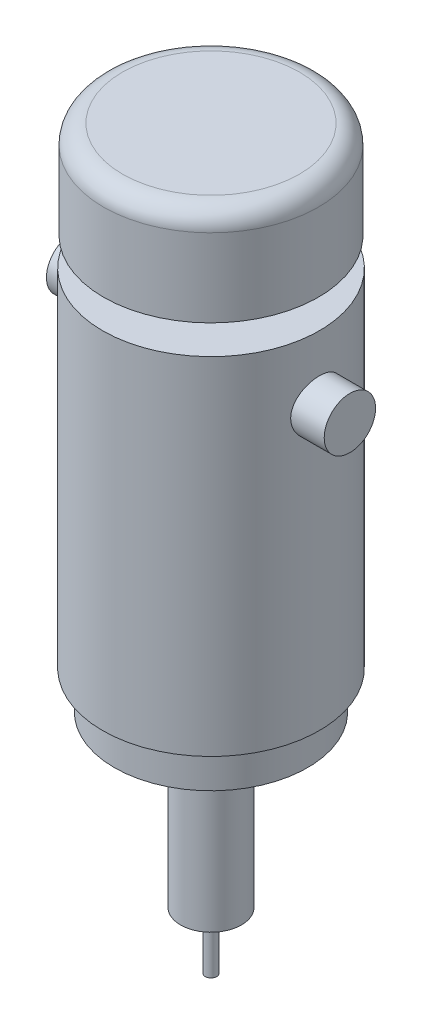
SolidWorks part; units mm, degrees
ref_plane "Front Plane" through (0, 0, 0) normal (0, 0, 1) x (1, 0, 0)
ref_plane "Top Plane" through (0, 0, 0) normal (0, 1, 0) x (1, 0, 0)
ref_plane "Right Plane" through (0, 0, 0) normal (1, 0, 0) x (0, 0, -1)
sketch "Sketch1" plane through (0, 0, 0) normal (0, 1, 0) x (1, 0, 0)
  circle A0 centre (0, 0) radius 28.5
  dimension "D1" = 57
extrude "Boss-Extrude1" add sketch "Sketch1" along normal mid plane 91
sketch "Sketch4" plane through (0, -45.5, 0) normal (0, -1, 0) x (1, 0, 0)
  circle A0 centre (0, 0) radius 25.4
  dimension "D1" = 50.8
extrude "Boss-Extrude4" add sketch "Sketch4" along normal blind 10
sketch "Sketch5" plane through (0, -55.5, 0) normal (0, -1, 0) x (1, 0, 0)
  circle A0 centre (0, 0) radius 12.65
  dimension "D1" = 25.3
extrude "Boss-Extrude5" add sketch "Sketch5" along normal blind 2.5
sketch "Sketch2" plane through (0, -58, 0) normal (0, -1, 0) x (1, 0, 0)
  circle A0 centre (0, 0) radius 8
  dimension "D1" = 16
extrude "Boss-Extrude2" add sketch "Sketch2" along normal blind 42
sketch "Sketch6" plane through (0, 45.5, 0) normal (0, 1, 0) x (1, 0, 0)
  circle A0 centre (0, 0) radius 4
  dimension "D1" = 8
extrude "Boss-Extrude6" add sketch "Sketch6" along normal blind 33
sketch "Sketch7" plane through (0, 78.5, 0) normal (0, 1, 0) x (1, 0, 0)
  circle A0 centre (0, 0) radius 28.25
  dimension "D1" = 56.5
extrude "Boss-Extrude7" add sketch "Sketch7" against normal blind 25.5
fillet "Fillet1" radius 5 1 edges at (0, 78.5, 28.25)
sketch "Sketch3" plane through (0, -100, 0) normal (0, -1, 0) x (1, 0, 0)
  circle A0 centre (0, 0) radius 1.5
  dimension "D1" = 3
extrude "Boss-Extrude3" add sketch "Sketch3" along normal blind 15
sketch "Sketch8" plane through (0, 0, 0) normal (1, 0, 0) x (0, 0, -1)
  line L0 (28.5, 45.5) -> (-28.5, 45.5) construction
  line L1 (0, 0) -> (0, 73.5) construction
  line L2 (-28.25, 73.5) -> (28.25, 73.5) construction
  circle A0 centre (0, 28.5) radius 6.75
  dimension "D1" = 13.5
  dimension "D2" = 17
extrude "Boss-Extrude8" add sketch "Sketch8" along normal mid plane 73
